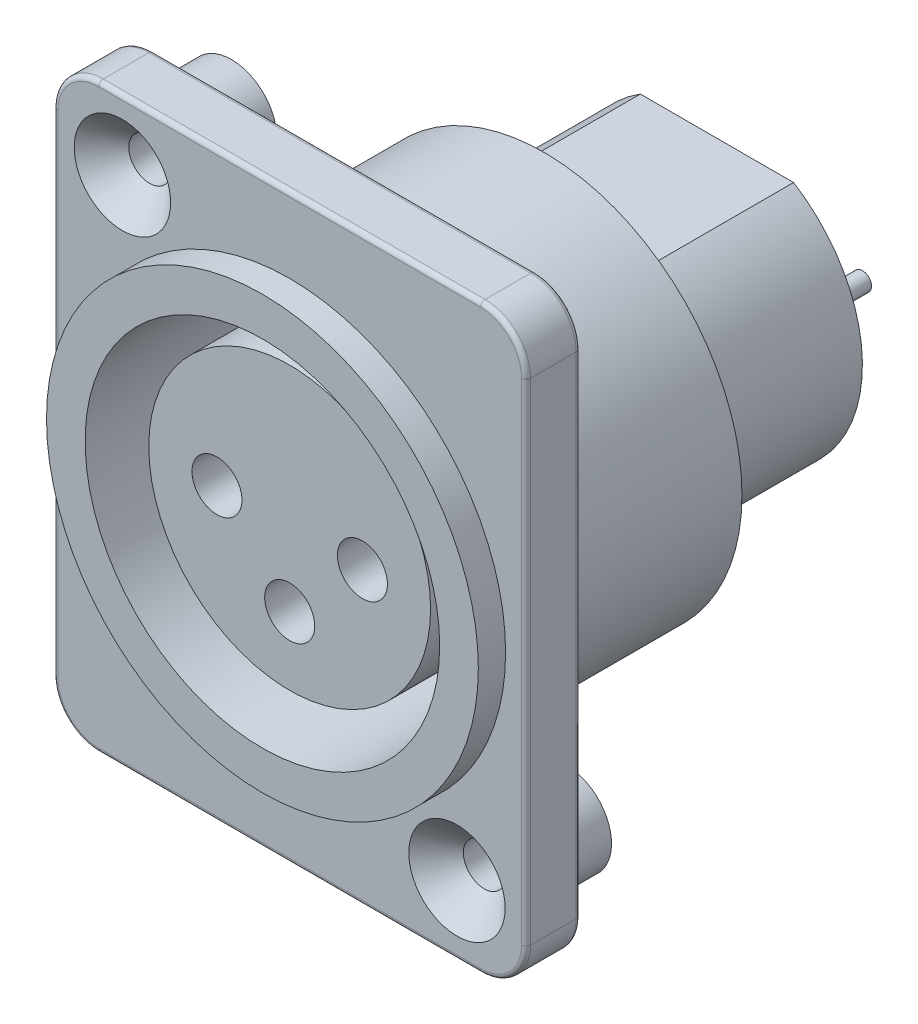
SolidWorks part; units mm, degrees
ref_plane "Alzado" through (0, 0, 0) normal (0, 0, 1) x (1, 0, 0)
ref_plane "Planta" through (0, 0, 0) normal (0, 1, 0) x (1, 0, 0)
ref_plane "Vista lateral" through (0, 0, 0) normal (1, 0, 0) x (0, 0, -1)
sketch "Croquis1" plane through (0, 0, 0) normal (0, 0, 1) x (1, 0, 0)
  line L0 (-4.2143, 6.8) -> (4.2143, 6.8)
  arc A0 (-4.2143, 6.8) -> (4.2143, 6.8) centre (0, 0) ccw
  dimension "D1" = 8
  dimension "D2" = 6.8
extrude "Saliente-Extruir1" add sketch "Croquis1" along normal blind 9.5
sketch "Croquis2" plane through (0, 0, 9.5) normal (0, 0, 1) x (1, 0, 0)
  circle A0 centre (0, 0) radius 10.875
  dimension "D1" = 21.75
extrude "Saliente-Extruir2" add sketch "Croquis2" along normal blind 11
sketch "Croquis3" plane through (0, 0, 20.5) normal (0, 0, 1) x (1, 0, 0)
  line L1 (13, -16) -> (-13, -16)
  line L2 (13, -16) -> (13, 16)
  line L3 (13, 16) -> (-13, 16)
  line L4 (-13, -16) -> (-13, 16)
  line L5 (13, -16) -> (-13, 16) construction
  line L6 (13, 16) -> (-13, -16) construction
  point P0 (0, 0)
  dimension "D1" = 26
  dimension "D2" = 32
extrude "Saliente-Extruir3" add sketch "Croquis3" along normal blind 3
fillet "Redondeo1" radius 2.5 4 edges at (13, -16, 22) (-13, -16, 22) (-13, 16, 22) (13, 16, 22)
sketch "Croquis4" plane through (0, 0, 23.5) normal (0, 0, 1) x (1, 0, 0)
  line L0 (-4, 0) -> (0, 0) construction
  line L1 (0, 0) -> (4, 0) construction
  line L2 (0, 0) -> (0, -4) construction
  circle A0 centre (0, 0) radius 9.75
  circle A1 centre (0, 0) radius 7.75
  circle A2 centre (0, 0) radius 11.875
  circle A3 centre (-4, 0) radius 1.375
  circle A4 centre (0, -4) radius 1.375
  circle A5 centre (4, 0) radius 1.375
  dimension "D1" = 19.5
  dimension "D2" = 23.75
  dimension "D3" = 15.5
  dimension "D4" = 2.75
  dimension "D5" = 4
extrude "Saliente-Extruir4" add sketch "Croquis4" along normal blind 1.5 contours A2 A0 region at (-11.5391, 0, 23.5)
extrude "Cortar-Extruir1" cut sketch "Croquis4<3>" against normal blind 10 contours A3 | A4 | A5 | A0 A1 region at (-9.4742, 0, 23.5) region at (-4, 0, 23.5) region at (0, -4, 23.5) region at (4, 0, 23.5)
sketch "Croquis4<3>" plane through (0, 0, 23.5) normal (0, 0, 1) x (1, 0, 0) same geometry as "Croquis4"
sketch "Croquis5" plane through (0, 0, 23.5) normal (0, 0, 1) x (1, 0, 0)
  line L0 (-9.2, 12.2) -> (9.2, -12.2) construction
  line L1 (9.2, -12.2) -> (9.2, -13.35) construction
  line L2 (-9.2, 13.35) -> (-9.2, 16) construction
  line L3 (-10.5, -16) -> (10.5, -16) construction
  line L4 (10.5, 16) -> (-10.5, 16) construction
  line L5 (10.35, -12.2) -> (13, -12.2) construction
  line L6 (13, -13.5) -> (13, 13.5) construction
  circle A0 centre (-9.2, 12.2) radius 1.15
  circle A1 centre (9.2, -12.2) radius 1.15
  dimension "D2" = 2.3
  dimension "D1" = 2.65
  dimension "D3" = 2.65
extrude "Cortar-Extruir2" cut sketch "Croquis5" against normal up to next
chamfer "Chaflán1" distance 1.5 angle 45 2 edges at (10.35, -12.2, 23.5) (-8.05, 12.2, 23.5)
sketch "Croquis6" plane through (0, 0, 0) normal (0, 0, -1) x (-1, 0, 0)
  circle A0 centre (-4, 0) radius 1.375 construction
  circle A1 centre (4, 0) radius 1.375 construction
  circle A2 centre (0, -4) radius 1.375 construction
  circle A3 centre (-4, 0) radius 1.375
  circle A4 centre (4, 0) radius 1.375
  circle A5 centre (0, -4) radius 1.375
  circle A6 centre (-4, 0) radius 0.5
  circle A7 centre (0, -4) radius 0.5
  circle A8 centre (4, 0) radius 0.5
  dimension "D1" = 1
extrude "Saliente-Extruir5" add sketch "Croquis6" along normal blind 1 contours A6 | A3 A6 | A8 | A4 A8 | A5 A7 | A7 region at (5.3361, 0, 0) region at (-2.6639, 0, 0) region at (1.3361, -4, 0) region at (4, 0, 0) region at (0, -4, 0) region at (-4, 0, 0)
extrude "Saliente-Extruir6" add sketch "Croquis6<3>" along normal blind 4 contours A6 | A8 | A7
sketch "Croquis6<3>" plane through (0, 0, 0) normal (0, 0, -1) x (-1, 0, 0) same geometry as "Croquis6"
fillet "Redondeo2" radius 0.25 16 edges at (12.2678, 15.2678, 20.5) (13, 0, 20.5) (12.2678, -15.2678, 20.5) (0, -16, 20.5) (-12.2678, -15.2678, 20.5) (-13, 0, 20.5) (-12.2678, 15.2678, 20.5) (12.2678, 15.2678, 23.5) (13, 0, 23.5) (12.2678, -15.2678, 23.5) (0, -16, 23.5) (-12.2678, -15.2678, 23.5) (-13, 0, 23.5) (-12.2678, 15.2678, 23.5) (0, 16, 20.5) (0, 16, 23.5)
sketch "Croquis7" plane through (0, 0, 20.5) normal (0, 0, -1) x (-1, 0, 0)
  circle A0 centre (9.2, 12.2) radius 1.15 construction
  circle A1 centre (-9.2, -12.2) radius 1.15 construction
  circle A2 centre (9.2, 12.2) radius 1.15
  circle A3 centre (-9.2, -12.2) radius 1.15
  circle A4 centre (-9.2, -12.2) radius 2.5
  circle A5 centre (9.2, 12.2) radius 2.5
  dimension "D1" = 5
extrude "Saliente-Extruir7" add sketch "Croquis7" along normal blind 3
